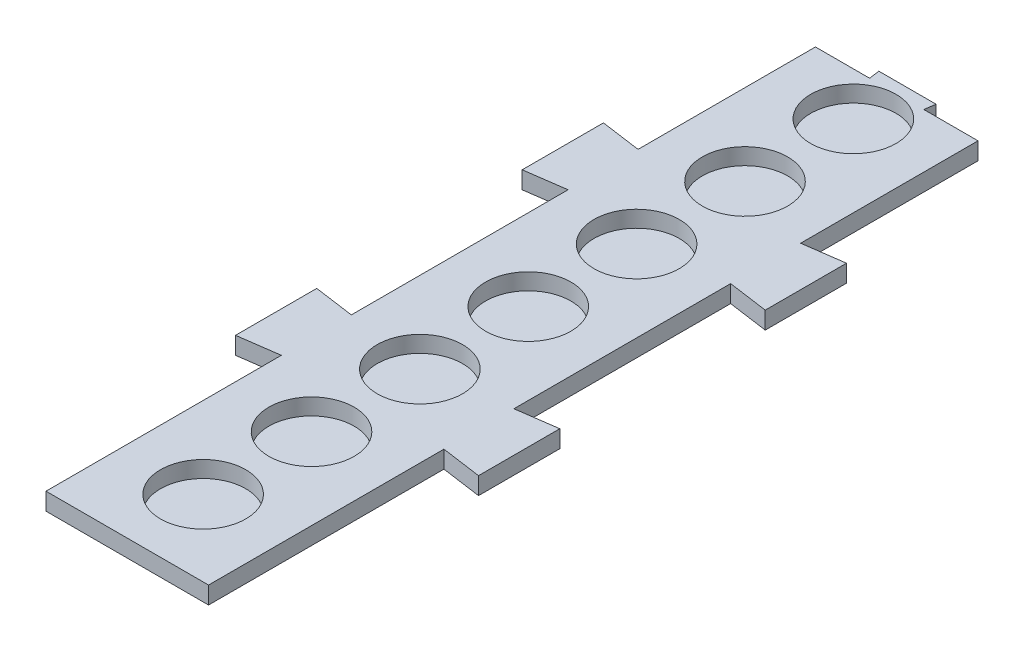
SolidWorks part; units mm, degrees
ref_plane "Front Plane" through (0, 0, 0) normal (0, 0, 1) x (1, 0, 0)
ref_plane "Top Plane" through (0, 0, 0) normal (0, 1, 0) x (1, 0, 0)
ref_plane "Right Plane" through (0, 0, 0) normal (1, 0, 0) x (0, 0, -1)
sketch "Sketch1" plane through (0, 0, 0) normal (0, 1, 0) x (1, 0, 0)
  line L1 (-19.05, -195.58) -> (19.05, -195.58)
  line L2 (-19.05, -195.58) -> (-19.05, 195.58)
  line L3 (-19.05, 195.58) -> (19.05, 195.58)
  line L4 (19.05, -195.58) -> (19.05, 195.58)
  line L5 (-19.05, -195.58) -> (19.05, 195.58) construction
  line L6 (-19.05, 195.58) -> (19.05, -195.58) construction
  point P0 (0, 0)
  dimension "D1" = 391.16
  dimension "D2" = 38.1
extrude "Boss-Extrude1" add sketch "Sketch1" along normal blind 4.064
sketch "Sketch2" plane through (0, 4.064, 0) normal (0, 1, 0) x (1, 0, 0)
  line L0 (-19.05, 195.58) -> (-19.05, -195.58) construction
  line L1 (19.05, 195.58) -> (-19.05, 195.58) construction
  line L3 (-19.05, -195.58) -> (19.05, -195.58) construction
  circle A0 centre (0, 177.8) radius 10
  circle A1 centre (0, 152.4) radius 10
  circle A2 centre (0, 127) radius 10
  circle A3 centre (0, 101.6) radius 10
  circle A4 centre (0, 76.2) radius 10
  circle A5 centre (0, 50.8) radius 10
  circle A6 centre (0, 25.4) radius 10
  circle A7 centre (0, 0) radius 10
  circle A8 centre (0, -25.4) radius 10
  circle A9 centre (0, -50.8) radius 10
  circle A10 centre (0, -76.2) radius 10
  circle A11 centre (0, -101.6) radius 10
  circle A12 centre (0, -127) radius 10
  circle A13 centre (0, -152.4) radius 10
  circle A14 centre (0, -177.8) radius 10
  dimension "D1" = 20
  dimension "D2" = 19.05
  dimension "D4" = 17.78
  dimension "D5" = 17.78
  dimension "D3" = 15
extrude "Cut-Extrude1" cut sketch "Sketch2" against normal blind 3.864
sketch "Sketch4" plane through (0, 0, 0) normal (0, 1, 0) x (1, 0, 0)
  line L0 (19.05, -56.8163) -> (28.4823, -55.4906)
  line L2 (19.05, -195.58) -> (19.05, 195.58) construction
  line L5 (19.05, 144.78) -> (19.05, 128.3812)
  line L6 (0, 195.58) -> (0, -195.58) construction
  line L7 (19.05, 195.58) -> (-19.05, 195.58) construction
  line L8 (-19.05, -195.58) -> (19.05, -195.58) construction
  line L9 (19.05, -56.8163) -> (19.05, -73.215)
  line L30 (-19.05, 144.78) -> (-19.05, 128.3812)
  line L31 (19.05, 144.78) -> (28.4823, 146.1056)
  line L32 (-19.05, 128.3812) -> (-28.4823, 127.0556)
  line L33 (19.05, 128.3812) -> (28.4823, 127.0556)
  line L34 (28.4823, 146.1056) -> (28.4823, 127.0556)
  line L35 (19.05, 144.78) -> (19.05, 128.3812)
  line L36 (19.05, 144.78) -> (19.05, 128.3812)
  line L37 (28.4823, 127.0556) -> (28.4823, 146.1056)
  line L38 (19.05, 144.78) -> (28.4823, 146.1056)
  line L39 (-19.05, 144.78) -> (-28.4823, 146.1056)
  line L40 (-28.4823, 127.0556) -> (-28.4823, 146.1056)
  line L41 (-28.4823, 146.1056) -> (-28.4823, 127.0556)
  line L42 (19.05, 77.5812) -> (28.4823, 78.9069)
  line L43 (19.05, 77.5812) -> (19.05, 61.1825)
  line L44 (19.05, 61.1825) -> (28.4823, 59.8569)
  line L45 (28.4823, 78.9069) -> (28.4823, 59.8569)
  line L46 (19.05, 10.3825) -> (28.4823, 11.7081)
  line L47 (19.05, 10.3825) -> (19.05, -6.0163)
  line L48 (19.05, -6.0163) -> (28.4823, -7.3419)
  line L49 (28.4823, 11.7081) -> (28.4823, -7.3419)
  line L50 (-19.05, 10.3825) -> (-19.05, -6.0163)
  line L51 (-19.05, -6.0163) -> (-28.4823, -7.3419)
  line L52 (-28.4823, 11.7081) -> (-28.4823, -7.3419)
  line L53 (-19.05, 10.3825) -> (-28.4823, 11.7081)
  line L54 (-19.05, 77.5812) -> (-19.05, 61.1825)
  line L55 (-19.05, 61.1825) -> (-28.4823, 59.8569)
  line L56 (-28.4823, 78.9069) -> (-28.4823, 59.8569)
  line L57 (-19.05, 77.5812) -> (-28.4823, 78.9069)
  line L58 (19.05, -73.215) -> (28.4823, -74.5406)
  line L59 (28.4823, -55.4906) -> (28.4823, -74.5406)
  line L60 (19.05, -124.015) -> (28.4823, -122.6894)
  line L61 (19.05, -124.015) -> (19.05, -140.4138)
  line L62 (19.05, -140.4138) -> (28.4823, -141.7394)
  line L63 (28.4823, -122.6894) -> (28.4823, -141.7394)
  line L72 (-19.05, -124.015) -> (-19.05, -140.4138)
  line L73 (-19.05, -140.4138) -> (-28.4823, -141.7394)
  line L74 (-28.4823, -122.6894) -> (-28.4823, -141.7394)
  line L75 (-19.05, -124.015) -> (-28.4823, -122.6894)
  line L76 (-19.05, -56.8163) -> (-19.05, -73.215)
  line L77 (-19.05, -73.215) -> (-28.4823, -74.5406)
  line L78 (-28.4823, -55.4906) -> (-28.4823, -74.5406)
  line L79 (-19.05, -56.8163) -> (-28.4823, -55.4906)
  line L80 (19.05, 144.78) -> (28.4823, 144.78) construction
  line L81 (19.05, 128.3812) -> (28.4823, 128.3812) construction
  dimension "D1" = 8
  dimension "D2" = 8
  dimension "D3" = 9.525
  dimension "D4" = 19.05
  dimension "D5" = 50.8
  dimension "D6" = 5
  dimension "D7" = 50.8
extrude "Boss-Extrude2" add sketch "Sketch4" along normal blind 4.064 contours L54 L57 L56 L55 | L50 L53 L52 L51 | L49 L46 L47 L48 | L40 L32 L30 L39 | L34 L31 L5 L33 | L45 L44 L43 L42 | L76 L77 L78 L79 | L0 L59 L58 L9 | L60 L63 L62 L61 | L72 L73 L74 L75 region at (23.8837, 0, -136.5806) region at (-23.8837, 0, -136.5806) region at (23.8837, 0, -2.1831) region at (-23.8837, 0, -2.1831) region at (-23.8837, 0, -69.3819)
sketch "Sketch6" [suppressed] plane through (0, 4.064, 0) normal (0, 1, 0) x (1, 0, 0)
  line L0 (-7.2424, -12.7) -> (-6.35, -19.05)
  line L1 (19.05, -12.7) -> (-19.05, -12.7) construction
  line L2 (-6.35, -19.05) -> (-19.05, -19.05)
  line L3 (-19.05, -19.05) -> (-19.05, -12.7)
  line L4 (-7.2424, -12.7) -> (-7.2424, -19.05) construction
  line L5 (19.05, -12.7) -> (19.05, -19.05)
  line L6 (19.05, -19.05) -> (6.35, -19.05)
  line L7 (6.35, -19.05) -> (7.2424, -12.7)
  line L8 (7.2424, -12.7) -> (7.2424, -19.05) construction
  line L9 (-19.05, -12.7) -> (-7.2424, -12.7)
  line L10 (7.2424, -12.7) -> (19.05, -12.7)
  dimension "D1" = 8
  dimension "D2" = 12.7
  dimension "D3" = 6.35
  dimension "D4" = 8
  dimension "D5" = 6.35
  dimension "D6" = 12.7
extrude "Boss-Extrude3" [suppressed] add sketch "Sketch6" against normal blind 4.064
sketch "Sketch7" plane through (0, 0, -195.58) normal (0, 0, -1) x (-1, 0, 0)
  line L1 (-28.4823, 4.064) -> (28.4823, 4.064)
  line L2 (-28.4823, 4.064) -> (-28.4823, 0)
  line L3 (-28.4823, 0) -> (28.4823, 0)
  line L4 (28.4823, 4.064) -> (28.4823, 0)
extrude "Cut-Extrude2" cut sketch "Sketch7" against normal blind 210.82
sketch "Sketch8" plane through (0, 4.064, 0) normal (0, 1, 0) x (1, 0, 0)
  line L0 (-6.35, -15.24) -> (-6.7035, -12.7247)
  line L1 (-19.05, -15.24) -> (19.05, -15.24) construction
  line L2 (-6.7035, -12.7247) -> (6.7035, -12.7247)
  line L3 (6.7035, -12.7247) -> (6.35, -15.24)
  line L4 (6.35, -15.24) -> (-6.35, -15.24)
  line L5 (-6.35, -15.24) -> (-6.35, -12.7247) construction
  line L6 (6.35, -15.24) -> (6.35, -12.7247) construction
  dimension "D1" = 8
  dimension "D2" = 8
  dimension "D3" = 12.7
  dimension "D4" = 12.7
  dimension "D5" = 2.54
extrude "Boss-Extrude4" add sketch "Sketch8" against normal blind 4.064
sketch "Sketch9" plane through (0, 0, 15.24) normal (0, 0, -1) x (-1, 0, 0)
  line L0 (-28.4823, 4.064) -> (-28.4823, 0) construction
  line L2 (28.4823, 4.064) -> (28.4823, 0) construction
  line L3 (-19.05, 0) -> (-6.35, 0) construction
  line L4 (6.35, 0) -> (19.05, 0) construction
  circle A0 centre (12.6073, 2.032) radius 1.27
  circle A1 centre (-12.6073, 2.032) radius 1.27
  dimension "D3" = 2.54
  dimension "D4" = 2.54
  dimension "D1" = 15.875
  dimension "D2" = 15.875
  dimension "D5" = 2.032
  dimension "D6" = 2.032
extrude "Cut-Extrude3" cut sketch "Sketch9" against normal blind 12.7
